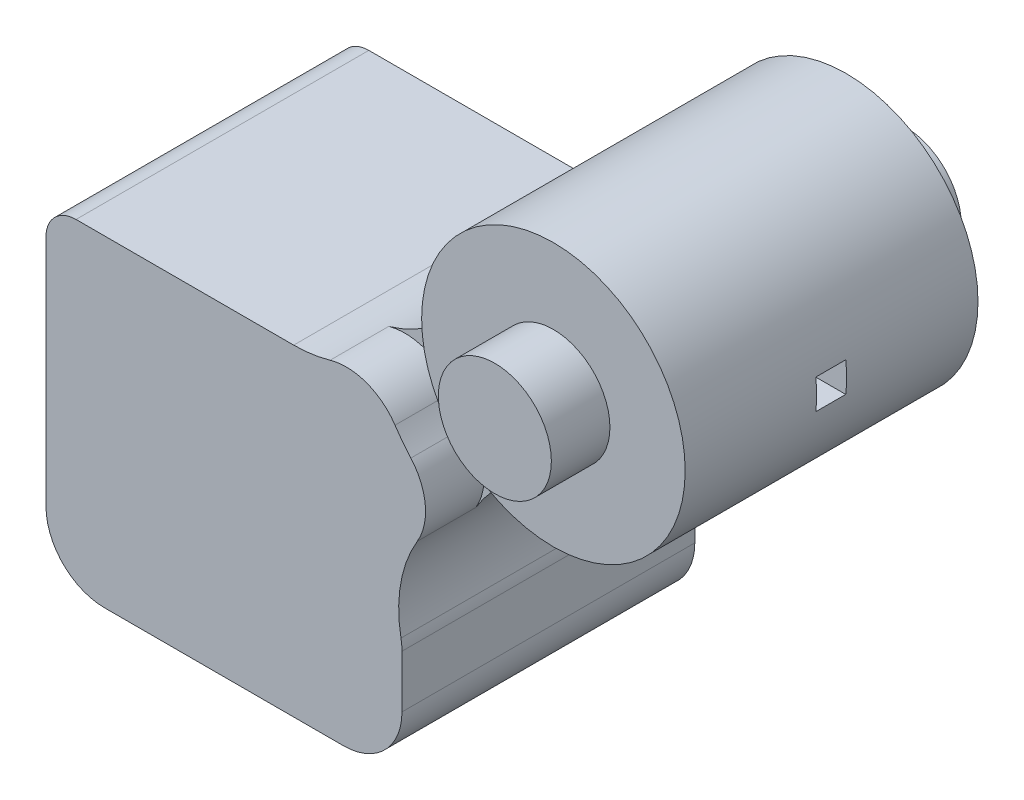
SolidWorks part; units mm, degrees
material "ABS"
ref_plane "Front Plane" through (0, 0, 0) normal (0, 0, 1) x (1, 0, 0)
ref_plane "Top Plane" through (0, 0, 0) normal (0, 1, 0) x (1, 0, 0)
ref_plane "Right Plane" through (0, 0, 0) normal (1, 0, 0) x (0, 0, -1)
sketch "Sketch1" plane through (0, 0, 0) normal (0, 0, 1) x (1, 0, 0)
  line L0 (5.5562, 0) -> (16.6687, 0)
  line L1 (0, 5.5562) -> (22.225, 5.5562)
  line L4 (22.225, 5.5562) -> (22.225, -5.5562) construction
  line L5 (0, 5.5562) -> (22.225, 5.5562) construction
  line L9 (13.1316, 0.7956) -> (22.225, 0) construction
  line L10 (22.225, 0) -> (22.225, -9.1281) construction
  line L11 (5.5562, 0) -> (0, 0)
  line L12 (0, 0) -> (0, 5.5562)
  line L13 (13.7542, 7.9121) -> (13.1316, 0.7956) construction
  circle A0 centre (0, 0) radius 5.5562 construction
  circle A1 centre (22.225, 0) radius 5.5562 construction
  circle A2 centre (22.225, -9.1281) radius 3.5719
  arc A3 (22.225, -5.5562) -> (22.225, 5.5562) centre (22.225, 0) ccw
  circle A5 centre (22.225, 0) radius 1.7859
  circle A6 centre (22.225, -9.1281) radius 1.7859
  arc A7 (16.6687, 0) -> (22.225, -5.5562) centre (22.225, 0) ccw
  circle A23 centre (22.225, 0) radius 9.1281 construction
  circle A30 centre (2.7781, 2.7781) radius 2.7781
  circle A31 centre (0.8137, 4.7426) radius 0.8137
  circle A32 centre (13.1316, 0.7956) radius 1.7859
  circle A33 centre (13.1316, 0.7956) radius 3.5719
  circle A34 centre (13.7542, 7.9121) radius 1.7859
  circle A35 centre (13.7542, 7.9121) radius 3.5719
  arc A36 (14.9108, 0.6399) -> (22.225, -7.3422) centre (22.225, 0) ccw
  arc A37 (22.225, -10.9141) -> (11.3525, 0.9512) centre (22.225, 0) cw
  arc A38 (22.225, -12.7) -> (9.5733, 1.1069) centre (22.225, 0) cw
  dimension "D1" = 22.225
  dimension "D2" = 11.1125
  dimension "D3" = 3.5719
  dimension "D5" = 7.1437
  dimension "D4" = 95
sketch "Sketch3" plane through (0, 0, 0) normal (0, 0, 1) x (1, 0, 0)
  line L0 (0.8137, 5.5562) -> (11.0694, 5.5562)
  line L1 (0, 5.5562) -> (22.225, 5.5562) construction
  line L2 (0, 4.7426) -> (0, 2.7781)
  line L3 (2.7781, 0) -> (9.6495, 0)
  line L4 (5.5562, 0) -> (16.6687, 0) construction
  line L5 (0, 2.7781) -> (0, 0)
  line L6 (0, 0) -> (2.7781, 0)
  line L7 (0, 0) -> (0, -3.175)
  line L8 (0, -3.175) -> (9.6495, -3.175)
  line L9 (9.6495, -3.175) -> (9.6495, 0)
  circle A0 centre (13.1316, 0.7956) radius 3.5719
  circle A1 centre (13.7542, 7.9121) radius 3.5719
  circle A2 centre (13.7542, 7.9121) radius 1.5319
  circle A3 centre (13.1316, 0.7956) radius 3.5719 construction
  circle A5 centre (13.7542, 7.9121) radius 3.5719 construction
  circle A6 centre (0.8137, 4.7426) radius 0.8137 construction
  circle A7 centre (0.8137, 4.7426) radius 0.8137
  circle A8 centre (2.7781, 2.7781) radius 2.7781
  dimension "D2" = 3.0639
  dimension "D1" = 3.175
extrude "Boss-Extrude1" add sketch "Sketch3" along normal blind 7.9375 contours A8 L3 A0 A1 L0 | A1 A2 | A8 A7 | A8 A7 L2 | A8 A7 | A7 A8 | A8 L0 A7 | A8 L5 L6 | L8 L9 L3 L6 L7 region at (0.5853, 4.9709, 0) region at (1.6395, 5.4598, 0) region at (7.8103, 3.0306, 0) region at (2.8496, 2.7066, 0) region at (0.0964, 3.9168, 0) region at (1.0724, 4.4838, 0) region at (12.5311, 11.1603, 0) region at (0.6205, 0.6205, 0) region at (4.8247, -1.5875, 0)
extrude "Boss-Extrude2" add sketch "Sketch3<4>" along normal blind 9.525 and the other way blind 1.5875 contours A2 region at (13.7542, 7.9121, 0)
sketch "Sketch3<4>" plane through (0, 0, 0) normal (0, 0, 1) x (1, 0, 0) same geometry as "Sketch3"
fillet "Fillet1" radius 1.5875 3 edges at (9.6495, 0, 3.9688) (9.6495, -3.175, 3.9688) (0, -3.175, 3.9688)
sketch "Sketch4" plane through (0, -3.175, 0) normal (0, -1, 0) x (1, 0, 0)
  line L0 (4.8247, 7.9375) -> (4.8247, 0) construction
  line L2 (4.031, 1.5875) -> (5.6185, 1.5875)
  line L3 (4.031, 1.5875) -> (4.031, 6.35)
  line L4 (1.5875, 0) -> (8.062, 0)
  line L5 (8.062, 0) -> (8.062, 7.9375)
  line L6 (8.062, 7.9375) -> (1.5875, 7.9375)
  line L7 (1.5875, 7.9375) -> (1.5875, 0)
  line L8 (1.5875, 0) -> (8.062, 0) construction
  line L9 (8.062, 0) -> (8.062, 7.9375) construction
  line L10 (8.062, 7.9375) -> (1.5875, 7.9375) construction
  line L11 (1.5875, 7.9375) -> (1.5875, 0) construction
  line L12 (4.031, 6.35) -> (5.6185, 6.35)
  line L13 (5.6185, 1.5875) -> (5.6185, 6.35)
  line L14 (4.031, 1.5875) -> (5.6185, 6.35) construction
  line L15 (4.031, 6.35) -> (5.6185, 1.5875) construction
  point P6 (4.8247, 3.9688)
  dimension "D2" = 1.5875
  dimension "D3" = 4.7625
  dimension "D1" = 0
extrude "Cut-Extrude1" cut sketch "Sketch4" against normal blind 3.175
sketch "Sketch5" plane through (0, 0, 0) normal (-1, 0, 0) x (0, 0, 1)
  line L0 (0, 1.5775) -> (7.9375, 1.5775) construction
  line L5 (0, 4.7426) -> (7.9375, 4.7426) construction
  line L6 (0, 4.7426) -> (0, -1.5875) construction
  line L7 (0, -1.5875) -> (7.9375, -1.5875) construction
  line L8 (7.9375, 4.7426) -> (7.9375, -1.5875) construction
  line L10 (1.5812, 0.7838) -> (6.3564, 0.7838)
  line L11 (1.5812, 0.7838) -> (1.5812, 2.3713)
  line L12 (1.5812, 2.3713) -> (6.3564, 2.3713)
  line L13 (6.3564, 0.7838) -> (6.3564, 2.3713)
  line L14 (1.5812, 0.7838) -> (6.3564, 2.3713) construction
  line L15 (1.5812, 2.3713) -> (6.3564, 0.7838) construction
  point P8 (3.9688, 1.5775)
  dimension "D1" = 1.5875
  dimension "D2" = 4.7752
extrude "Cut-Extrude2" cut sketch "Sketch5" against normal blind 3.175
fillet "Fillet2" radius 3.5719 1 edges at (11.0694, 5.5562, 3.9688)
ref_plane "Plane1" through (17.3261, 0, 0) normal (1, 0, 0) x (0, 0, -1)
sketch "Sketch6" plane through (17.3261, 0, 0) normal (1, 0, 0) x (0, 0, -1)
  line L0 (-9.525, 7.9121) -> (1.5875, 7.9121) construction
  line L1 (-9.525, 9.4441) -> (-9.525, 6.3802) construction
  line L2 (1.5875, 6.3802) -> (1.5875, 9.4441) construction
  line L4 (-4.3752, 7.5057) -> (-3.5624, 7.5057)
  line L5 (-4.3752, 7.5057) -> (-4.3752, 8.3185)
  line L6 (-4.3752, 8.3185) -> (-3.5624, 8.3185)
  line L7 (-3.5624, 7.5057) -> (-3.5624, 8.3185)
  line L8 (-4.3752, 7.5057) -> (-3.5624, 8.3185) construction
  line L9 (-4.3752, 8.3185) -> (-3.5624, 7.5057) construction
  circle A0 centre (-3.9688, 7.9121) radius 0.4064
  point P12 (-3.5624, 7.5057)
  dimension "D1" = 0.8128
extrude "Cut-Extrude4" cut sketch "Sketch6" against normal blind 0.8928 contours A0 | A0 L4 L7 | A0 L5 L4 | A0 L6 L5 | A0 L7 L6 region at (17.3261, 7.5965, 4.2844) region at (17.3261, 7.5965, 3.6531) region at (17.3261, 7.9121, 3.9688) region at (17.3261, 8.2278, 4.2844) region at (17.3261, 8.2278, 3.6531)
sketch "Sketch7" plane through (0, 0, 7.9375) normal (0, 0, 1) x (1, 0, 0)
  circle A0 centre (13.7542, 7.9121) radius 3.5719
  circle A1 centre (13.7542, 7.9121) radius 5.1594
  arc A2 (13.4429, 4.3539) -> (10.2345, 8.5201) centre (13.7542, 7.9121) ccw construction
  arc A3 (13.4429, 4.3539) -> (9.6219, 0.1323) centre (13.1316, 0.7956) ccw construction
  arc A4 (6.7147, 5.5562) -> (10.2345, 8.5201) centre (6.7147, 9.1281) ccw construction
  arc A5 (13.4429, 4.3539) -> (10.9204, 3.6007) centre (13.1316, 0.7956) ccw
  arc A6 (8.8619, 6.2737) -> (10.2345, 8.5201) centre (6.7147, 9.1281) ccw
  arc M5 (9.6219, 0.1323) -> (13.4429, 4.3539) centre (13.1316, 0.7956) cw
  arc M7 (10.2345, 8.5201) -> (6.7147, 5.5562) centre (6.7147, 9.1281) cw
  dimension "D1" = 1.5875
extrude "Cut-Extrude6" cut sketch "Sketch7" against normal blind 1.5875 contours A1 A0 M7 M5 region at (10.4618, 5.3767, 7.9375)
extrude "Cut-Extrude7" cut sketch "Sketch7<6>" against normal blind 1.5875 from offset 6.35 contours A1 A0 M7 M5 region at (10.4618, 5.3767, 7.9375) offset against normal yes
sketch "Sketch7<6>" plane through (0, 0, 7.9375) normal (0, 0, 1) x (1, 0, 0) same geometry as "Sketch7"
fillet "Fillet4" radius 1.5875 4 edges at (10.9204, 3.6007, 0.7938) (10.9204, 3.6007, 7.1437) (8.8619, 6.2737, 7.1437) (8.8619, 6.2737, 0.7938)
